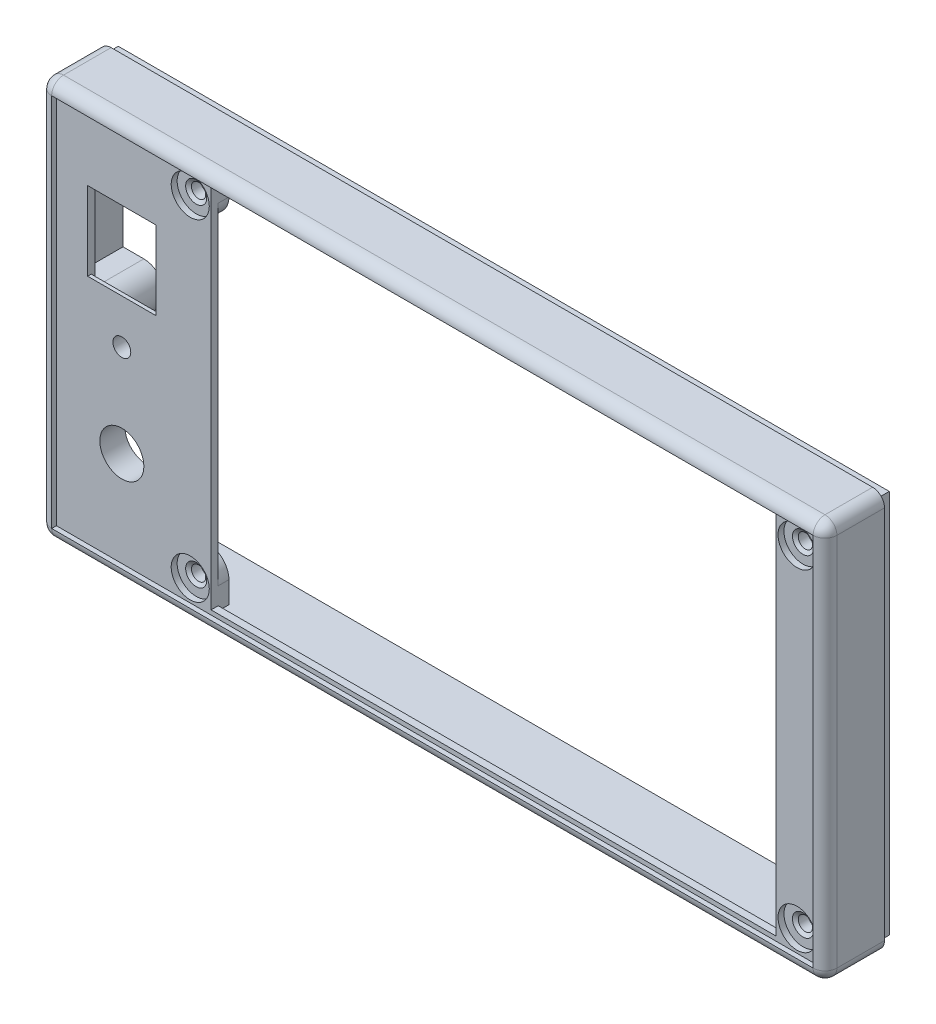
SolidWorks part; units mm, degrees
ref_plane "Спереди" through (0, 0, 0) normal (0, 0, 1) x (1, 0, 0)
ref_plane "Сверху" through (0, 0, 0) normal (0, 1, 0) x (1, 0, 0)
ref_plane "Справа" through (0, 0, 0) normal (1, 0, 0) x (0, 0, -1)
sketch "Эскиз1" plane through (0, 0, 0) normal (0, 0, 1) x (1, 0, 0)
  line L1 (-35.4452, 29.8258) -> (96.5548, 29.8258)
  line L2 (-35.4452, 29.8258) -> (-35.4452, -37.1742)
  line L3 (-35.4452, -37.1742) -> (96.5548, -37.1742)
  line L4 (96.5548, 29.8258) -> (96.5548, -37.1742)
  dimension "D1" = 67
  dimension "D2" = 132
extrude "Бобышка-Вытянуть1" add sketch "Эскиз1" against normal blind 10
shell "Оболочка1" thickness 2 removed face at (30.5548, -3.6742, -10) removed face at (30.5548, -3.6742, 0)
sketch "Эскиз3" plane through (0, 0, -10) normal (0, 0, -1) x (-1, 0, 0)
  line L1 (-96.5548, 29.8258) -> (35.4452, 29.8258)
  line L2 (-96.5548, 29.8258) -> (-96.5548, -37.1742)
  line L3 (-96.5548, -37.1742) -> (35.4452, -37.1742)
  line L4 (35.4452, 29.8258) -> (35.4452, -37.1742)
  line L5 (34.6452, -36.3742) -> (-95.7548, -36.3742)
  line L6 (34.6452, -36.3742) -> (34.6452, 29.0258)
  line L7 (34.6452, 29.0258) -> (-95.7548, 29.0258)
  line L8 (-95.7548, -36.3742) -> (-95.7548, 29.0258)
  dimension "D1" = 0.8
  dimension "D2" = 0.8
  dimension "D3" = 0.8
  dimension "D4" = 0.8
extrude "Бобышка-Вытянуть2" add sketch "Эскиз3" along normal blind 2
sketch "Эскиз4" plane through (0, 0, 0) normal (0, 0, 1) x (1, 0, 0)
  line L1 (-35.4452, 29.8258) -> (96.5548, 29.8258)
  line L2 (-35.4452, 29.8258) -> (-35.4452, -37.1742)
  line L3 (-35.4452, -37.1742) -> (96.5548, -37.1742)
  line L4 (96.5548, 29.8258) -> (96.5548, -37.1742)
extrude "Бобышка-Вытянуть3" add sketch "Эскиз4" against normal blind 2
sketch "Эскиз5" plane through (0, 0, -2) normal (0, 0, -1) x (-1, 0, 0)
  line L0 (33.4452, 27.8258) -> (-94.5548, 27.8258) construction
  line L1 (-85.5548, 24.8258) -> (-0.5548, 24.8258)
  line L2 (-85.5548, 24.8258) -> (-85.5548, -32.1742)
  line L3 (-85.5548, -32.1742) -> (-0.5548, -32.1742)
  line L4 (-0.5548, 24.8258) -> (-0.5548, -32.1742)
  line L5 (-94.5548, -35.1742) -> (33.4452, -35.1742) construction
  line L6 (-94.5548, 27.8258) -> (-94.5548, -35.1742) construction
  dimension "D1" = 3
  dimension "D2" = 3
  dimension "D3" = 9
  dimension "D4" = 85
  dimension "D5" = 57
extrude "Вырез-Вытянуть2" cut sketch "Эскиз5" against normal blind 2
sketch "Эскиз6" plane through (0, 0, -2) normal (0, 0, -1) x (-1, 0, 0)
  circle A0 centre (21.9452, -3.6742) radius 3.5
  dimension "D1" = 7
extrude "Вырез-Вытянуть3" cut sketch "Эскиз6" against normal blind 2
sketch "Эскиз7" plane through (0, 0, 0) normal (0, 0, 1) x (1, 0, 0)
  line L5 (-32.9452, 27.3258) -> (94.0548, 27.3258)
  line L6 (-32.9452, 27.3258) -> (-32.9452, -34.6742)
  line L7 (-32.9452, -34.6742) -> (94.0548, -34.6742)
  line L8 (94.0548, 27.3258) -> (94.0548, -34.6742)
extrude "Вырез-Вытянуть4" cut sketch "Эскиз7" against normal blind 0.8
sketch "Эскиз8" plane through (95.7548, 0, 0) normal (-1, 0, 0) x (0, 0, 1)
  line L1 (-11.2, 23.4258) -> (-12, 23.4258)
  line L2 (-11.2, 23.4258) -> (-11.2, 5.6258)
  line L3 (-11.2, 5.6258) -> (-12, 5.6258)
  line L4 (-12, 23.4258) -> (-12, 5.6258)
  line L5 (-11.2, -12.9742) -> (-12, -12.9742)
  line L6 (-11.2, -12.9742) -> (-11.2, -30.7742)
  line L7 (-11.2, -30.7742) -> (-12, -30.7742)
  line L8 (-12, -12.9742) -> (-12, -30.7742)
  dimension "D1" = 17.8
  dimension "D2" = 17.8
extrude "Бобышка-Вытянуть4" add sketch "Эскиз8" along normal blind 1.2
sketch "Эскиз9" plane through (0, 0, -12) normal (0, 0, -1) x (-1, 0, 0)
  line L1 (-94.5548, 27.8258) -> (33.4452, 27.8258)
  line L2 (-94.5548, 27.8258) -> (-94.5548, -35.1742)
  line L3 (-94.5548, -35.1742) -> (33.4452, -35.1742)
  line L4 (33.4452, 27.8258) -> (33.4452, -35.1742)
  line L5 (34.6452, -36.3742) -> (-95.7548, -36.3742)
  line L6 (34.6452, -36.3742) -> (34.6452, 29.0258)
  line L7 (34.6452, 29.0258) -> (-95.7548, 29.0258)
  line L8 (-95.7548, -36.3742) -> (-95.7548, 29.0258)
extrude "Бобышка-Вытянуть5" add sketch "Эскиз9" against normal blind 2
sketch "Эскиз10" plane through (0, 0, -12) normal (0, 0, -1) x (-1, 0, 0)
  line L0 (33.4452, 27.8258) -> (-94.5548, 27.8258) construction
  line L1 (-96.5548, 29.8258) -> (35.4452, 29.8258)
  line L2 (-96.5548, 29.8258) -> (-96.5548, -37.1742)
  line L3 (-96.5548, -37.1742) -> (35.4452, -37.1742)
  line L4 (35.4452, 29.8258) -> (35.4452, -37.1742)
  line L5 (34.2452, -35.9742) -> (-95.3548, -35.9742)
  line L6 (34.2452, -35.9742) -> (34.2452, 28.6258)
  line L7 (34.2452, 28.6258) -> (-95.3548, 28.6258)
  line L8 (-95.3548, -35.9742) -> (-95.3548, 28.6258)
  line L9 (-94.5548, 27.8258) -> (-94.5548, -35.1742) construction
  line L10 (-94.5548, -35.1742) -> (33.4452, -35.1742) construction
  line L11 (33.4452, -35.1742) -> (33.4452, 27.8258) construction
  dimension "D1" = 0.8
  dimension "D2" = 0.8
  dimension "D3" = 0.8
  dimension "D4" = 0.8
extrude "Вырез-Вытянуть5" cut sketch "Эскиз10" against normal blind 2
sketch "Эскиз11" plane through (0, 0, -2) normal (0, 0, -1) x (-1, 0, 0)
  line L0 (-94.5548, 27.8258) -> (-94.5548, -35.1742) construction
  line L1 (-87.0548, 27.0758) -> (7.9452, 27.0758)
  line L2 (-87.0548, 27.0758) -> (-87.0548, -34.4242)
  line L3 (-87.0548, -34.4242) -> (7.9452, -34.4242)
  line L4 (7.9452, 27.0758) -> (7.9452, -34.4242)
  line L5 (33.4452, 27.8258) -> (-94.5548, 27.8258) construction
  line L6 (-94.5548, -35.1742) -> (33.4452, -35.1742) construction
  dimension "D1" = 7.5
  dimension "D2" = 95
  dimension "D3" = 0.75
  dimension "D4" = 0.75
  dimension "D5" = 61.5
extrude "Вырез-Вытянуть6" cut sketch "Эскиз11" against normal blind 2
sketch "Эскиз12" plane through (0, 0, 0) normal (0, 0, 1) x (1, 0, 0)
  line L0 (96.5548, -37.1742) -> (96.5548, 29.8258) construction
  line L1 (-33.4452, 27.8258) -> (94.5548, 27.8258)
  line L2 (-33.4452, 27.8258) -> (-33.4452, -35.1742)
  line L3 (-33.4452, -35.1742) -> (94.5548, -35.1742)
  line L4 (94.5548, 27.8258) -> (94.5548, -35.1742)
  line L5 (-35.4452, -37.1742) -> (96.5548, -37.1742) construction
  line L6 (-35.4452, 29.8258) -> (-35.4452, -37.1742) construction
  line L7 (96.5548, 29.8258) -> (-35.4452, 29.8258) construction
  dimension "D1" = 2
  dimension "D2" = 2
  dimension "D3" = 2
  dimension "D4" = 2
extrude "Вырез-Вытянуть7" cut sketch "Эскиз12" against normal blind 0.8
sketch "Эскиз14" plane through (0, 0, -2) normal (0, 0, -1) x (-1, 0, 0)
  line L0 (33.4452, 27.8258) -> (-94.5548, 27.8258) construction
  line L1 (-94.5548, -35.1742) -> (33.4452, -35.1742) construction
  line L2 (-94.5548, -28.0242) -> (-94.5548, -35.1742)
  line L3 (-94.5548, 27.8258) -> (-94.5548, -35.1742) construction
  line L4 (7.9452, -34.4242) -> (7.9452, 27.0758) construction
  line L5 (-87.0548, 27.0758) -> (-87.0548, -34.4242) construction
  line L6 (-94.5548, -35.1742) -> (-87.5548, -35.1742)
  line L7 (-87.5548, -35.1742) -> (-87.5548, -31.5242)
  line L9 (-91.0548, -28.0242) -> (-94.5548, -28.0242)
  line L11 (-87.5548, 24.1758) -> (-87.5548, 27.8258)
  line L12 (-87.5548, 27.8258) -> (-94.5548, 27.8258)
  line L13 (-94.5548, 27.8258) -> (-94.5548, 20.6758)
  line L14 (-94.5548, 20.6758) -> (-91.0548, 20.6758)
  line L15 (7.4452, 24.1758) -> (7.4452, 27.8258)
  line L16 (7.4452, 27.8258) -> (14.4452, 27.8258)
  line L17 (33.4452, 27.8258) -> (-94.5548, 27.8258) construction
  line L18 (14.4452, 27.8258) -> (14.4452, 24.1758)
  line L19 (7.4452, -31.5242) -> (7.4452, -35.1742)
  line L20 (7.4452, -35.1742) -> (14.4452, -35.1742)
  line L21 (-94.5548, -35.1742) -> (33.4452, -35.1742) construction
  line L22 (14.4452, -35.1742) -> (14.4452, -31.5242)
  circle A0 centre (-91.0548, 24.1758) radius 1.2
  circle A1 centre (-91.0548, -31.5242) radius 1.2
  circle A2 centre (10.9452, 24.1758) radius 1.2
  circle A3 centre (10.9452, -31.5242) radius 1.2
  arc A4 (-91.0548, -28.0242) -> (-87.5548, -31.5242) centre (-91.0548, -31.5242) cw
  arc A5 (-87.5548, 24.1758) -> (-91.0548, 20.6758) centre (-91.0548, 24.1758) cw
  arc A6 (7.4452, 24.1758) -> (14.4452, 24.1758) centre (10.9452, 24.1758) ccw
  arc A7 (14.4452, -31.5242) -> (7.4452, -31.5242) centre (10.9452, -31.5242) ccw
  dimension "D1" = 3.65
  dimension "D2" = 3.65
  dimension "D5" = 3.5
  dimension "D6" = 3.5
  dimension "D7" = 102
  dimension "D8" = 102
  dimension "D9" = 55.7
  dimension "D10" = 3
  dimension "D11" = 4
extrude "Бобышка-Вытянуть6" add sketch "Эскиз14" along normal blind 1.8
sketch "Эскиз15" plane through (0, 0, -0.8) normal (0, 0, 1) x (1, 0, 0)
  line L1 (-7.9452, 27.0758) -> (-7.4452, 27.0758)
  line L2 (-7.9452, 27.0758) -> (-7.9452, -34.4242)
  line L3 (-7.9452, -34.4242) -> (-7.4452, -34.4242)
  line L4 (-7.4452, 27.0758) -> (-7.4452, -34.4242)
extrude "Бобышка-Вытянуть7" add sketch "Эскиз15" against normal up to surface (1.2 mm away) up to face at (-7.6645, -32.515, -2)
sketch "Эскиз16" plane through (0, 0, -2) normal (0, 0, -1) x (-1, 0, 0)
  line L0 (-87.5548, -35.1742) -> (-87.5548, -31.5242) construction
  line L1 (-87.0548, 27.0758) -> (-87.5548, 27.0758)
  line L2 (-87.0548, 27.0758) -> (-87.0548, -34.4242)
  line L3 (-87.0548, -34.4242) -> (-87.5548, -34.4242)
  line L4 (-87.5548, 27.0758) -> (-87.5548, -34.4242)
extrude "Вырез-Вытянуть8" cut sketch "Эскиз16" against normal blind 1.8
sketch "Эскиз17" plane through (0, 0, -2) normal (0, 0, -1) x (-1, 0, 0)
  circle A0 centre (-91.0548, 24.1758) radius 1.2
  circle A1 centre (-91.0548, -31.5242) radius 1.2
  circle A2 centre (10.9452, -31.5242) radius 1.2
  circle A5 centre (10.9452, 24.1758) radius 1.2
extrude "Вырез-Вытянуть9" cut sketch "Эскиз17" against normal blind 1.8
sketch "Эскиз19" plane through (0, 0, -2) normal (0, 0, -1) x (-1, 0, 0)
  line L0 (33.4452, -35.1742) -> (33.4452, 27.8258) construction
  line L1 (14.4452, -35.1742) -> (33.4452, -35.1742) construction
  line L2 (14.4452, -35.1742) -> (14.4452, -31.5242) construction
  circle A0 centre (22.4452, -19.1742) radius 3.5
  point P8 (14.4452, -33.3492)
  dimension "D1" = 11
  dimension "D2" = 16
  dimension "D3" = 8
extrude "Вырез-Вытянуть11" cut sketch "Эскиз19" against normal blind 1.8
sketch "Эскиз22" plane through (0, 0, -2) normal (0, 0, -1) x (-1, 0, 0)
  circle A0 centre (21.9452, -3.6742) radius 3.5
extrude "Бобышка-Вытянуть9" add sketch "Эскиз22" against normal up to surface (1.2 mm away) up to face at (-18.9452, -19.1742, -0.8)
sketch "Эскиз23" plane through (0, 0, -2) normal (0, 0, -1) x (-1, 0, 0)
  line L2 (16.6952, 2.5758) -> (28.1952, 2.5758)
  line L3 (16.6952, 2.5758) -> (16.6952, 17.5758)
  line L4 (16.6952, 17.5758) -> (28.1952, 17.5758)
  line L5 (28.1952, 2.5758) -> (28.1952, 17.5758)
  circle A2 centre (22.4452, -3.6742) radius 1.5
  dimension "D5" = 11.5
  dimension "D7" = 15
extrude "Вырез-Вытянуть13" cut sketch "Эскиз23" against normal blind 1.8
sketch "Эскиз24" plane through (0, 0, -2) normal (0, 0, -1) x (-1, 0, 0)
  circle A0 centre (22.4452, -3.6742) radius 1.5
  circle A1 centre (22.4452, -3.6742) radius 2.5
extrude "Бобышка-Вытянуть10" add sketch "Эскиз24" along normal blind 1
chamfer "Фаска1" distance 2 angle 35 4 edges at (92.2548, -31.5242, -0.8) (92.2548, 24.1758, -0.8) (-9.7452, -31.5242, -0.8) (-9.7452, 24.1758, -0.8) first distance on face at (-22.4452, 10.0758, -0.8)
sketch "Эскиз25" plane through (0, 0, -2) normal (0, 0, -1) x (-1, 0, 0)
  line L0 (33.4452, -35.1742) -> (33.4452, 27.8258) construction
  line L1 (29.9452, -0.1742) -> (33.4452, -0.1742)
  line L2 (33.4452, -35.1742) -> (33.4452, 27.8258) construction
  line L3 (33.4452, -0.1742) -> (33.4452, -7.1742)
  line L4 (33.4452, -7.1742) -> (29.9452, -7.1742)
  arc A0 (29.9452, -0.1742) -> (29.9452, -7.1742) centre (29.9452, -3.6742) ccw
  circle A1 centre (29.9452, -3.6742) radius 1.2
  dimension "D1" = 3.5
extrude "Бобышка-Вытянуть11" add sketch "Эскиз25" along normal up to surface (10 mm away) up to face at (30.5548, -3.6742, -12)
sketch "Эскиз26" plane through (95.3548, 0, 0) normal (1, 0, 0) x (0, 0, -1)
  line L0 (10, 28.6258) -> (10, -35.9742) construction
  line L1 (10, 18.8258) -> (11.2, 18.8258)
  line L2 (10, 18.8258) -> (10, 3.2258)
  line L3 (10, 3.2258) -> (11.2, 3.2258)
  line L4 (11.2, 18.8258) -> (11.2, 3.2258)
  line L5 (10, 28.6258) -> (12, 28.6258) construction
  line L6 (10, -35.9742) -> (12, -35.9742) construction
  line L7 (10, -26.1742) -> (11.2, -26.1742)
  line L8 (10, -26.1742) -> (10, -10.5742)
  line L9 (10, -10.5742) -> (11.2, -10.5742)
  line L10 (11.2, -26.1742) -> (11.2, -10.5742)
  dimension "D1" = 9.8
  dimension "D2" = 15.6
  dimension "D3" = 1.2
  dimension "D4" = 9.8
  dimension "D5" = 15.6
  dimension "D6" = 1.2
  dimension "D7" = 13.8
extrude "Вырез-Вытянуть14" cut sketch "Эскиз26" against normal blind 10
sketch "Эскиз27" plane through (0, 0, -0.8) normal (0, 0, 1) x (1, 0, 0)
  line L0 (-16.6952, 2.5758) -> (-16.6952, 17.5758) construction
  line L1 (-28.1952, 17.5758) -> (-16.6952, 17.5758)
  line L2 (-28.1952, 17.5758) -> (-28.1952, 16.9758)
  line L3 (-28.1952, 16.9758) -> (-16.6952, 16.9758)
  line L4 (-16.6952, 17.5758) -> (-16.6952, 16.9758)
  line L6 (-28.1952, 2.5758) -> (-16.6952, 2.5758)
  line L7 (-28.1952, 2.5758) -> (-28.1952, 3.1758)
  line L8 (-28.1952, 3.1758) -> (-16.6952, 3.1758)
  line L9 (-16.6952, 2.5758) -> (-16.6952, 3.1758)
  dimension "D1" = 0.6
  dimension "D2" = 0.6
extrude "Бобышка-Вытянуть12" add sketch "Эскиз27" against normal blind 0.6
fillet "Скругление1" radius 2 8 edges at (96.5548, 29.8258, -5) (96.5548, -37.1742, -5) (96.5548, -3.6742, 0) (30.5548, 29.8258, 0) (-35.4452, 29.8258, -5) (-35.4452, -37.1742, -5) (30.5548, -37.1742, 0) (-35.4452, -3.6742, 0)
sketch "Эскиз28" plane through (0, 0, -2) normal (0, 0, -1) x (-1, 0, 0)
  circle A0 centre (22.4452, -19.1742) radius 3.7
extrude "Вырез-Вытянуть15" cut sketch "Эскиз28" against normal blind 10
sketch "Эскиз29" plane through (0, 0, -2) normal (0, 0, -1) x (-1, 0, 0)
  circle A0 centre (22.4452, -19.1742) radius 3.7
  circle A1 centre (22.4452, -19.1742) radius 5.7
extrude "Бобышка-Вытянуть13" add sketch "Эскиз29" along normal blind 3
sketch "Эскиз30" plane through (0, 0, -1.4) normal (0, 0, -1) x (-1, 0, 0)
  line L1 (16.6952, 2.5758) -> (28.1952, 2.5758)
  line L2 (16.6952, 2.5758) -> (16.6952, 3.1758)
  line L3 (16.6952, 3.1758) -> (28.1952, 3.1758)
  line L4 (28.1952, 2.5758) -> (28.1952, 3.1758)
extrude "Бобышка-Вытянуть14" add sketch "Эскиз30" along normal up to surface (0.6 mm away) up to face at (-19.9452, -3.6742, -2)
sketch "Эскиз32" plane through (0, 0, -0.8) normal (0, 0, 1) x (1, 0, 0)
  line L0 (-16.6952, 3.1758) -> (-16.6952, 16.9758) construction
  line L1 (-28.1952, 3.1758) -> (-16.6952, 3.1758)
  line L2 (-28.1952, 3.1758) -> (-28.1952, 3.7758)
  line L3 (-28.1952, 3.7758) -> (-16.6952, 3.7758)
  line L4 (-16.6952, 3.1758) -> (-16.6952, 3.7758)
  dimension "D1" = 0.6
extrude "Бобышка-Вытянуть15" add sketch "Эскиз32" against normal blind 0.6
sketch "Эскиз33" plane through (94.5548, 0, 0) normal (-1, 0, 0) x (0, 0, 1)
  line L0 (-10, 3.2258) -> (-11.2, 3.2258) construction
  line L1 (-11.2, 18.8258) -> (-11, 18.8258)
  line L2 (-11.2, 18.8258) -> (-11.2, 3.2258)
  line L3 (-11.2, 3.2258) -> (-11, 3.2258)
  line L4 (-11, 18.8258) -> (-11, 3.2258)
  line L5 (-10, -26.1742) -> (-11.2, -26.1742) construction
  line L6 (-11.2, -10.5742) -> (-11, -10.5742)
  line L7 (-11.2, -10.5742) -> (-11.2, -26.1742)
  line L8 (-11.2, -26.1742) -> (-11, -26.1742)
  line L9 (-11, -10.5742) -> (-11, -26.1742)
  dimension "D1" = 0.2
  dimension "D2" = 0.2
extrude "Бобышка-Вытянуть16" add sketch "Эскиз33" against normal up to surface (0.8 mm away) up to face at (95.3548, -3.6742, -10.7333)
sketch "Эскиз34" plane through (0, 0, -0.8) normal (0, 0, 1) x (1, 0, 0)
  circle A0 centre (-10.9452, 24.1758) radius 3.2
extrude "Вырез-Вытянуть16" cut sketch "Эскиз34" against normal blind 1
sketch "Эскиз35" plane through (0, 0, -0.8) normal (0, 0, 1) x (1, 0, 0)
  circle A0 centre (-10.9452, -31.5242) radius 3.2
  circle A1 centre (91.0548, -31.5242) radius 3.2
  circle A2 centre (91.0548, 24.1758) radius 3.2
extrude "Вырез-Вытянуть17" cut sketch "Эскиз35" against normal blind 1
